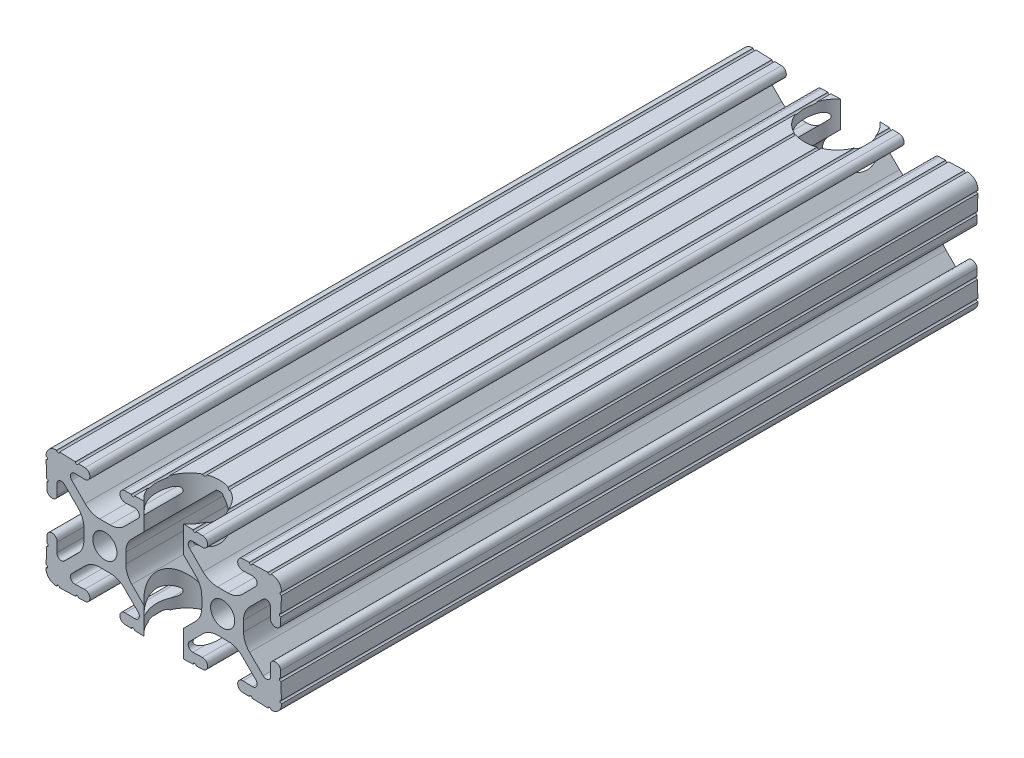
SolidWorks part; units mm, degrees
ref_plane "Front Plane" through (0, 0, 0) normal (0, 0, 1) x (1, 0, 0)
ref_plane "Top Plane" through (0, 0, 0) normal (0, 1, 0) x (1, 0, 0)
ref_plane "Right Plane" through (0, 0, 0) normal (1, 0, 0) x (0, 0, -1)
sketch "Sketch1" plane through (0, 0, 0) normal (0, 0, 1) x (1, 0, 0)
  line L0 (0, 12.7) -> (-12.7814, 12.7) construction
  line L1 (-4.5085, 0) -> (-4.5085, 2.9459)
  line L2 (-6.0437, 12.5461) -> (-10.0976, 12.6876) construction
  line L3 (-11.5616, 12.4229) -> (-4.3159, 12.1699) construction
  line L4 (-6.4364, 10.3486) -> (-6.3592, 12.5571) construction
  line L6 (-2.9459, 4.5085) -> (0, 4.5085)
  line L7 (0, 0) -> (0, 12.7) construction
  line L8 (0, 0) -> (-12.7814, 0) construction
  line L9 (0.7813, 0.7813) -> (-0.7813, -0.7813) construction
  line L10 (-2.9459, 4.5085) -> (-7.1484, 8.711)
  line L11 (-4.5085, 2.9459) -> (-8.711, 7.1484)
  line L13 (0, 0) -> (-12.7814, 12.7814) construction
  line L14 (-10.4131, 12.6987) -> (-4.3048, 12.4853)
  line L15 (-4.3048, 12.4853) -> (-4.382, 10.2769) construction
  line L16 (-4.382, 10.2769) -> (-6.4364, 10.3486)
  line L17 (-12.6987, 10.4131) -> (-12.4853, 4.3048)
  line L18 (-10.2769, 4.382) -> (-10.3486, 6.4364)
  circle A0 centre (0, 0) radius 2.6035
  arc A1 (-4.382, 10.2769) -> (-4.3048, 12.4853) centre (-4.3434, 11.3811) ccw
  arc A2 (-7.1484, 8.711) -> (-6.4364, 10.3486) centre (-6.4698, 9.3896) cw
  arc A3 (-8.711, 7.1484) -> (-10.3486, 6.4364) centre (-9.3896, 6.4698) ccw
  arc A4 (-10.2769, 4.382) -> (-12.4853, 4.3048) centre (-11.3811, 4.3434) cw
  arc A5 (-10.4131, 12.6987) -> (-12.6987, 10.4131) centre (-10.4902, 10.4902) ccw
  arc A6 (-10.4131, 12.6987) -> (-9.7821, 12.6766) centre (-10.0976, 12.6876) ccw
  arc A7 (-6.3592, 12.5571) -> (-5.7282, 12.5351) centre (-6.0437, 12.5461) ccw
  arc A8 (-12.5571, 6.3592) -> (-12.5351, 5.7282) centre (-12.5461, 6.0437) cw
  arc A9 (-12.6987, 10.4131) -> (-12.6766, 9.7821) centre (-12.6876, 10.0976) cw
  dimension "D1" = 5.207
  dimension "D5" = 14.859
  dimension "D9" = 2
  dimension "D2" = 25.4
  dimension "D12" = 0.6314
  dimension "D10" = 2.2098
  dimension "D3" = 9.017
  dimension "D4" = 9.017
  dimension "D6" = 25.4
  dimension "D7" = 6.477
  dimension "D8" = 2.2098
  dimension "D11" = 12.7
sketch "Sketch3" plane through (0, 0, 0) normal (0, 0, 1) x (1, 0, 0)
  line L0 (-2.9459, 4.5085) -> (0, 4.5085) construction
  line L1 (-2.9459, 4.5085) -> (-7.1484, 8.711) construction
  line L2 (-4.382, 10.2769) -> (-6.4364, 10.3486) construction
  line L3 (-10.4131, 12.6987) -> (-4.3048, 12.4853) construction
  line L4 (-4.5085, 0) -> (-4.5085, 2.9459) construction
  line L5 (-4.5085, 2.9459) -> (-8.711, 7.1484) construction
  line L6 (-10.2769, 4.382) -> (-10.3486, 6.4364) construction
  line L7 (-12.6987, 10.4131) -> (-12.4853, 4.3048) construction
  line L8 (-1.1153, 4.5085) -> (1.1153, 4.5085)
  line L9 (-4.2404, 5.803) -> (-7.1484, 8.711)
  line L10 (-4.382, 10.2769) -> (-6.4364, 10.3486)
  line L11 (-9.7821, 12.6766) -> (-6.3592, 12.5571)
  line L12 (-4.5085, -1.1153) -> (-4.5085, 1.1153)
  line L13 (-5.803, 4.2404) -> (-8.711, 7.1484)
  line L14 (-10.2769, 4.382) -> (-10.3486, 6.4364)
  line L15 (-12.6766, 9.7821) -> (-12.5571, 6.3592)
  line L16 (-5.7282, 12.5351) -> (-4.3048, 12.4853)
  line L17 (-12.5351, 5.7282) -> (-12.4853, 4.3048)
  line L18 (0, 0) -> (0, 12.7) construction
  line L19 (0, 0) -> (-12.7814, 0) construction
  line L20 (0, 0) -> (12.7, 0) construction
  line L21 (5.7282, 12.5351) -> (4.3048, 12.4853)
  line L22 (12.7, 10.5674) -> (12.7, 12.6987) construction
  line L23 (10.4131, 12.6987) -> (14.9869, 12.6987)
  line L24 (5.803, 4.2404) -> (12.1093, 10.5467)
  line L25 (4.5085, -1.1153) -> (4.5085, 1.1153)
  line L26 (9.7821, 12.6766) -> (6.3592, 12.5571)
  line L27 (4.382, 10.2769) -> (6.4364, 10.3486)
  line L28 (4.2404, 5.803) -> (7.1484, 8.711)
  line L29 (4.2404, -5.803) -> (7.1484, -8.711)
  line L30 (4.382, -10.2769) -> (6.4364, -10.3486)
  line L31 (9.7821, -12.6766) -> (6.3592, -12.5571)
  line L32 (5.803, -4.2404) -> (12.1093, -10.5467)
  line L33 (12.1093, 10.5467) -> (12.7, 10.5674)
  line L34 (10.4131, -12.6987) -> (14.9869, -12.6987)
  line L35 (5.7282, -12.5351) -> (4.3048, -12.4853)
  line L36 (12.7, -10.5674) -> (12.7, -12.6987) construction
  line L37 (-12.5351, -5.7282) -> (-12.4853, -4.3048)
  line L38 (-5.7282, -12.5351) -> (-4.3048, -12.4853)
  line L39 (-12.6766, -9.7821) -> (-12.5571, -6.3592)
  line L40 (-10.2769, -4.382) -> (-10.3486, -6.4364)
  line L41 (-5.803, -4.2404) -> (-8.711, -7.1484)
  line L42 (-9.7821, -12.6766) -> (-6.3592, -12.5571)
  line L43 (-4.382, -10.2769) -> (-6.4364, -10.3486)
  line L44 (-4.2404, -5.803) -> (-7.1484, -8.711)
  line L45 (-1.1153, -4.5085) -> (1.1153, -4.5085)
  line L46 (12.1093, -10.5467) -> (12.7, -10.5674)
  line L47 (13.2907, -10.5467) -> (12.7, -10.5674)
  line L48 (26.5153, -4.5085) -> (24.2847, -4.5085)
  line L49 (29.6404, -5.803) -> (32.5484, -8.711)
  line L50 (29.782, -10.2769) -> (31.8364, -10.3486)
  line L51 (35.1821, -12.6766) -> (31.7592, -12.5571)
  line L52 (31.203, -4.2404) -> (34.111, -7.1484)
  line L53 (35.6769, -4.382) -> (35.7486, -6.4364)
  line L54 (38.0766, -9.7821) -> (37.9571, -6.3592)
  line L55 (31.1282, -12.5351) -> (29.7048, -12.4853)
  line L56 (37.9351, -5.7282) -> (37.8853, -4.3048)
  line L57 (19.6718, -12.5351) -> (21.0952, -12.4853)
  line L58 (13.2907, 10.5467) -> (12.7, 10.5674)
  line L59 (19.597, -4.2404) -> (13.2907, -10.5467)
  line L60 (15.6179, -12.6766) -> (19.0408, -12.5571)
  line L61 (21.018, -10.2769) -> (18.9636, -10.3486)
  line L62 (21.1596, -5.803) -> (18.2516, -8.711)
  line L63 (21.1596, 5.803) -> (18.2516, 8.711)
  line L64 (21.018, 10.2769) -> (18.9636, 10.3486)
  line L65 (15.6179, 12.6766) -> (19.0408, 12.5571)
  line L66 (20.8915, -1.1153) -> (20.8915, 1.1153)
  line L67 (19.597, 4.2404) -> (13.2907, 10.5467)
  line L68 (19.6718, 12.5351) -> (21.0952, 12.4853)
  line L69 (37.9351, 5.7282) -> (37.8853, 4.3048)
  line L70 (31.1282, 12.5351) -> (29.7048, 12.4853)
  line L71 (38.0766, 9.7821) -> (37.9571, 6.3592)
  line L72 (35.6769, 4.382) -> (35.7486, 6.4364)
  line L73 (31.203, 4.2404) -> (34.111, 7.1484)
  line L74 (29.9085, -1.1153) -> (29.9085, 1.1153)
  line L75 (35.1821, 12.6766) -> (31.7592, 12.5571)
  line L76 (29.782, 10.2769) -> (31.8364, 10.3486)
  line L77 (29.6404, 5.803) -> (32.5484, 8.711)
  line L78 (26.5153, 4.5085) -> (24.2847, 4.5085)
  arc A0 (-10.4131, 12.6987) -> (-9.7821, 12.6766) centre (-10.0976, 12.6876) ccw construction
  arc A1 (-6.4364, 10.3486) -> (-7.1484, 8.711) centre (-6.4698, 9.3896) ccw construction
  arc A2 (-4.382, 10.2769) -> (-4.3048, 12.4853) centre (-4.3434, 11.3811) ccw construction
  arc A3 (-8.711, 7.1484) -> (-10.3486, 6.4364) centre (-9.3896, 6.4698) ccw construction
  arc A4 (-12.4853, 4.3048) -> (-10.2769, 4.382) centre (-11.3811, 4.3434) ccw construction
  arc A5 (-6.3592, 12.5571) -> (-5.7282, 12.5351) centre (-6.0437, 12.5461) ccw construction
  arc A6 (-10.4131, 12.6987) -> (-12.6987, 10.4131) centre (-10.4902, 10.4902) ccw construction
  arc A7 (-12.6766, 9.7821) -> (-12.6987, 10.4131) centre (-12.6876, 10.0976) ccw construction
  arc A8 (-12.5351, 5.7282) -> (-12.5571, 6.3592) centre (-12.5461, 6.0437) ccw construction
  arc A9 (-10.4131, 12.6987) -> (-9.7821, 12.6766) centre (-10.0976, 12.6876) ccw
  arc A10 (-6.4364, 10.3486) -> (-7.1484, 8.711) centre (-6.4698, 9.3896) ccw
  arc A11 (-4.382, 10.2769) -> (-4.3048, 12.4853) centre (-4.3434, 11.3811) ccw
  arc A12 (-8.711, 7.1484) -> (-10.3486, 6.4364) centre (-9.3896, 6.4698) ccw
  arc A13 (-12.4853, 4.3048) -> (-10.2769, 4.382) centre (-11.3811, 4.3434) ccw
  arc A14 (-6.3592, 12.5571) -> (-5.7282, 12.5351) centre (-6.0437, 12.5461) ccw
  arc A15 (-10.4131, 12.6987) -> (-12.6987, 10.4131) centre (-10.4902, 10.4902) ccw
  arc A16 (-12.6766, 9.7821) -> (-12.6987, 10.4131) centre (-12.6876, 10.0976) ccw
  arc A17 (-12.5351, 5.7282) -> (-12.5571, 6.3592) centre (-12.5461, 6.0437) ccw
  arc A18 (-1.1153, 4.5085) -> (-4.2404, 5.803) centre (-1.1153, 8.9281) cw
  arc A19 (4.5085, 1.1153) -> (5.803, 4.2404) centre (8.9281, 1.1153) cw
  arc A20 (1.1153, 4.5085) -> (4.2404, 5.803) centre (1.1153, 8.9281) ccw
  arc A21 (-4.5085, 1.1153) -> (-5.803, 4.2404) centre (-8.9281, 1.1153) ccw
  circle A22 centre (25.4, 0) radius 2.6035
  arc A23 (35.8131, -12.6987) -> (35.1821, -12.6766) centre (35.4976, -12.6876) ccw
  arc A24 (31.8364, -10.3486) -> (32.5484, -8.711) centre (31.8698, -9.3896) ccw
  arc A25 (6.3592, 12.5571) -> (5.7282, 12.5351) centre (6.0437, 12.5461) cw
  arc A26 (29.782, -10.2769) -> (29.7048, -12.4853) centre (29.7434, -11.3811) ccw
  arc A27 (34.111, -7.1484) -> (35.7486, -6.4364) centre (34.7896, -6.4698) ccw
  arc A28 (4.382, 10.2769) -> (4.3048, 12.4853) centre (4.3434, 11.3811) cw
  arc A29 (6.4364, 10.3486) -> (7.1484, 8.711) centre (6.4698, 9.3896) cw
  arc A30 (10.4131, 12.6987) -> (9.7821, 12.6766) centre (10.0976, 12.6876) cw
  arc A31 (10.4131, -12.6987) -> (9.7821, -12.6766) centre (10.0976, -12.6876) ccw
  arc A32 (6.4364, -10.3486) -> (7.1484, -8.711) centre (6.4698, -9.3896) ccw
  arc A33 (4.382, -10.2769) -> (4.3048, -12.4853) centre (4.3434, -11.3811) ccw
  arc A34 (37.8853, -4.3048) -> (35.6769, -4.382) centre (36.7811, -4.3434) ccw
  arc A35 (31.7592, -12.5571) -> (31.1282, -12.5351) centre (31.4437, -12.5461) ccw
  arc A36 (6.3592, -12.5571) -> (5.7282, -12.5351) centre (6.0437, -12.5461) ccw
  arc A37 (35.8131, -12.6987) -> (38.0987, -10.4131) centre (35.8902, -10.4902) ccw
  arc A38 (38.0766, -9.7821) -> (38.0987, -10.4131) centre (38.0876, -10.0976) ccw
  arc A39 (37.9351, -5.7282) -> (37.9571, -6.3592) centre (37.9461, -6.0437) ccw
  arc A40 (-4.5085, -1.1153) -> (-5.803, -4.2404) centre (-8.9281, -1.1153) cw
  arc A41 (1.1153, -4.5085) -> (4.2404, -5.803) centre (1.1153, -8.9281) cw
  arc A42 (4.5085, -1.1153) -> (5.803, -4.2404) centre (8.9281, -1.1153) ccw
  arc A43 (-1.1153, -4.5085) -> (-4.2404, -5.803) centre (-1.1153, -8.9281) ccw
  arc A44 (-12.5351, -5.7282) -> (-12.5571, -6.3592) centre (-12.5461, -6.0437) cw
  arc A45 (-12.6766, -9.7821) -> (-12.6987, -10.4131) centre (-12.6876, -10.0976) cw
  arc A46 (-10.4131, -12.6987) -> (-12.6987, -10.4131) centre (-10.4902, -10.4902) cw
  arc A47 (-6.3592, -12.5571) -> (-5.7282, -12.5351) centre (-6.0437, -12.5461) cw
  arc A48 (-12.4853, -4.3048) -> (-10.2769, -4.382) centre (-11.3811, -4.3434) cw
  arc A49 (-8.711, -7.1484) -> (-10.3486, -6.4364) centre (-9.3896, -6.4698) cw
  arc A50 (-4.382, -10.2769) -> (-4.3048, -12.4853) centre (-4.3434, -11.3811) cw
  arc A51 (-6.4364, -10.3486) -> (-7.1484, -8.711) centre (-6.4698, -9.3896) cw
  arc A52 (-10.4131, -12.6987) -> (-9.7821, -12.6766) centre (-10.0976, -12.6876) cw
  circle A53 centre (0, 0) radius 2.6035 construction
  circle A54 centre (0, 0) radius 2.6035
  arc A55 (26.5153, -4.5085) -> (29.6404, -5.803) centre (26.5153, -8.9281) cw
  arc A56 (20.8915, -1.1153) -> (19.597, -4.2404) centre (16.4719, -1.1153) cw
  arc A57 (24.2847, -4.5085) -> (21.1596, -5.803) centre (24.2847, -8.9281) ccw
  arc A58 (29.9085, -1.1153) -> (31.203, -4.2404) centre (34.3281, -1.1153) ccw
  arc A59 (19.0408, -12.5571) -> (19.6718, -12.5351) centre (19.3563, -12.5461) cw
  arc A60 (21.018, -10.2769) -> (21.0952, -12.4853) centre (21.0566, -11.3811) cw
  arc A61 (18.9636, -10.3486) -> (18.2516, -8.711) centre (18.9302, -9.3896) cw
  arc A62 (14.9869, -12.6987) -> (15.6179, -12.6766) centre (15.3024, -12.6876) cw
  arc A63 (14.9869, 12.6987) -> (15.6179, 12.6766) centre (15.3024, 12.6876) ccw
  arc A64 (18.9636, 10.3486) -> (18.2516, 8.711) centre (18.9302, 9.3896) ccw
  arc A65 (21.018, 10.2769) -> (21.0952, 12.4853) centre (21.0566, 11.3811) ccw
  arc A66 (19.0408, 12.5571) -> (19.6718, 12.5351) centre (19.3563, 12.5461) ccw
  arc A67 (29.9085, 1.1153) -> (31.203, 4.2404) centre (34.3281, 1.1153) cw
  arc A68 (24.2847, 4.5085) -> (21.1596, 5.803) centre (24.2847, 8.9281) cw
  arc A69 (20.8915, 1.1153) -> (19.597, 4.2404) centre (16.4719, 1.1153) ccw
  arc A70 (26.5153, 4.5085) -> (29.6404, 5.803) centre (26.5153, 8.9281) ccw
  arc A71 (37.9351, 5.7282) -> (37.9571, 6.3592) centre (37.9461, 6.0437) cw
  arc A72 (38.0766, 9.7821) -> (38.0987, 10.4131) centre (38.0876, 10.0976) cw
  arc A73 (35.8131, 12.6987) -> (38.0987, 10.4131) centre (35.8902, 10.4902) cw
  arc A74 (31.7592, 12.5571) -> (31.1282, 12.5351) centre (31.4437, 12.5461) cw
  arc A75 (37.8853, 4.3048) -> (35.6769, 4.382) centre (36.7811, 4.3434) cw
  arc A76 (34.111, 7.1484) -> (35.7486, 6.4364) centre (34.7896, 6.4698) cw
  arc A77 (29.782, 10.2769) -> (29.7048, 12.4853) centre (29.7434, 11.3811) cw
  arc A78 (31.8364, 10.3486) -> (32.5484, 8.711) centre (31.8698, 9.3896) cw
  arc A79 (35.8131, 12.6987) -> (35.1821, 12.6766) centre (35.4976, 12.6876) cw
  point P135 (4.5085, 0)
  point P218 (20.8915, 0)
  dimension "D2" = 4.4196
  dimension "D1" = 12.7
extrude "Extrude1" add sketch "Sketch3" along normal blind 190
sketch "Sketch4" plane through (0, 12.6987, 0) normal (0, 1, 0) x (1, 0, 0)
  line L0 (12.7, -190) -> (12.7, -164.6)
  line L1 (14.9869, -190) -> (10.4131, -190) construction
  line L2 (12.7, -164.6) -> (12.7, -24.9)
  circle A0 centre (12.7, -164.6) radius 6.75
  circle A1 centre (12.7, -24.9) radius 6.75
  line M2 (10.4131, 0) -> (10.4131, -190)
  line M4 (14.9869, -190) -> (14.9869, 0)
  dimension "D2" = 13.5
  dimension "D4" = 13.5
  dimension "D1" = 25.4
  dimension "D3" = 139.7
extrude "Cut-Extrude2" cut sketch "Sketch4" against normal through all contours A0 M4 | L0 A0 L2 M4 | A0 L0 L2 M2 | A0 M2 | A1 M4 | A1 M2 M4 | A1 M2 region at (11.568, 12.6987, 164.6) region at (13.832, 12.6987, 164.6) region at (8.565, 12.6987, 164.6) region at (16.835, 12.6987, 164.6) region at (11.5638, 12.6987, 31.409) region at (8.565, 12.6987, 24.9) region at (16.835, 12.6987, 24.9)
sketch "Sketch5" plane through (0, -12.6987, 0) normal (0, -1, 0) x (1, 0, 0)
  line L1 (-26.7303, 212.5424) -> (56.4213, 212.5424)
  line L2 (-26.7303, 212.5424) -> (-26.7303, 169.85)
  line L3 (-26.7303, 169.85) -> (56.4213, 169.85)
  line L4 (56.4213, 212.5424) -> (56.4213, 169.85)
  dimension "D1" = 1.5
extrude "Cut-Extrude3" cut sketch "Sketch5" against normal through all and the other way blind 10
sketch "Sketch6" plane through (0, 12.6987, 0) normal (0, 1, 0) x (1, 0, 0)
  line L1 (-22.4636, 21.4402) -> (45.6548, 21.4402)
  line L2 (-22.4636, 21.4402) -> (-22.4636, -19.65)
  line L3 (-22.4636, -19.65) -> (45.6548, -19.65)
  line L4 (45.6548, 21.4402) -> (45.6548, -19.65)
  dimension "D1" = 1.5
extrude "Cut-Extrude4" cut sketch "Sketch6" against normal through all and the other way through all
equation "\"D10@Sketch1\" = \"D8@Sketch1\""
equation "\"D11@Sketch1\" = \"D6@Sketch1\"/2"
equation "\"D12@Sketch1\" = \"D8@Sketch1\"/3.5"
equation "\"D2@Sketch3\" = \"D8@Sketch1\"*2"
